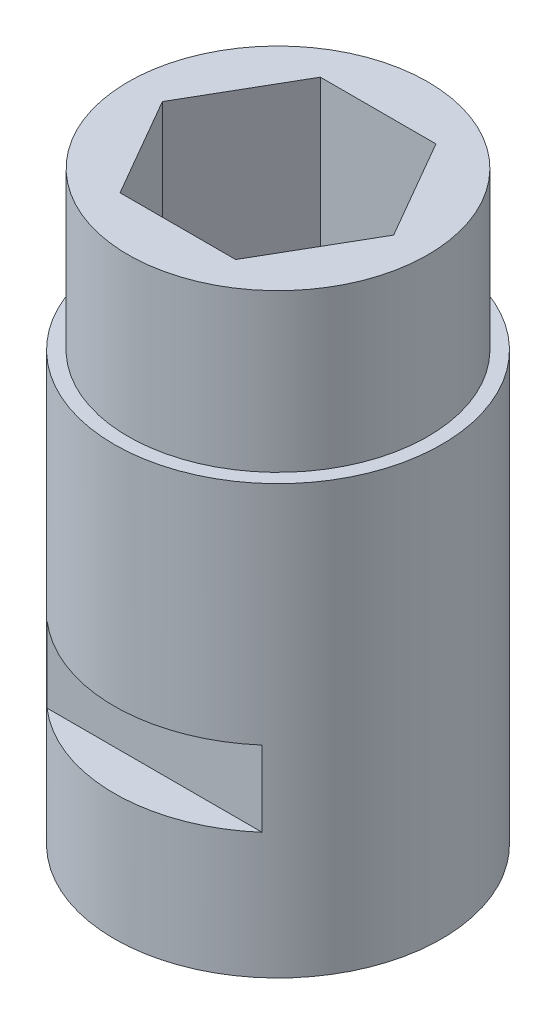
SolidWorks part; units mm, degrees
material "Polyester Resin"
ref_plane "Front Plane" through (0, 0, 0) normal (0, 0, 1) x (1, 0, 0)
ref_plane "Top Plane" through (0, 0, 0) normal (0, 1, 0) x (1, 0, 0)
ref_plane "Right Plane" through (0, 0, 0) normal (1, 0, 0) x (0, 0, -1)
sketch "Sketch1" plane through (0, 0, 0) normal (0, 1, 0) x (1, 0, 0)
  line L1 (-2.9156, 5.05) -> (-5.8312, 0)
  line L2 (-5.8312, 0) -> (-2.9156, -5.05)
  line L3 (-2.9156, -5.05) -> (2.9156, -5.05)
  line L4 (2.9156, -5.05) -> (5.8312, 0)
  line L5 (5.8312, 0) -> (2.9156, 5.05)
  line L6 (2.9156, 5.05) -> (-2.9156, 5.05)
  circle A0 centre (0, 0) radius 5.05 construction
  circle A1 centre (0, 0) radius 7.5565
  dimension "D2" = 15.113
  dimension "D1" = 10.1
extrude "Boss-Extrude1" add sketch "Sketch1" along normal blind 28.89
sketch "Sketch2" plane through (0, 0, 0) normal (0, -1, 0) x (1, 0, 0)
  circle A0 centre (0, 0) radius 7.5565
  circle A1 centre (0, 0) radius 3.3
  dimension "D1" = 6.6
extrude "Boss-Extrude2" add sketch "Sketch2" along normal blind 0.635
sketch "Sketch4" plane through (0, -0.635, 0) normal (0, -1, 0) x (1, 0, 0)
  circle A0 centre (0, 0) radius 7.5565
  circle A1 centre (0, 0) radius 8.255
  dimension "D1" = 16.51
extrude "Boss-Extrude3" add sketch "Sketch4" against normal blind 21.59
sketch "Sketch3" plane through (0, 0, 0) normal (1, 0, 0) x (0, 0, -1)
  line L0 (-6.223, 9.525) -> (-6.223, 5.715)
  line L1 (6.223, 9.525) -> (6.223, 5.715)
  line L2 (-7.5565, -0.635) -> (7.5565, -0.635) construction
  line L3 (-6.223, 9.525) -> (-8.3636, 9.525)
  line L4 (-8.3636, 9.525) -> (-8.3636, 5.715)
  line L5 (-8.3636, 5.715) -> (-6.223, 5.715)
  line L6 (6.223, 9.525) -> (8.4791, 9.525)
  line L7 (8.4791, 9.525) -> (8.4791, 5.715)
  line L8 (8.4791, 5.715) -> (6.223, 5.715)
  dimension "D1" = 12.446
  dimension "D2" = 6.223
  dimension "D3" = 3.81
  dimension "D4" = 3.81
  dimension "D5" = 6.35
  dimension "D6" = 6.35
extrude "Cut-Extrude1" cut sketch "Sketch3" against normal through all and the other way through all
equation "\"AB_Central_Bushing_Length\" = .75in"
equation "\"Solid_Length\"= .025in"
equation "\"Hex_Length\"=1.1374"
equation "\"D1@Boss-Extrude1\"= \"Hex_Length\""
equation "\"D1@Boss-Extrude2\"=\"Solid_Length\""
equation "\"Cutout_Angle\" = 80"
